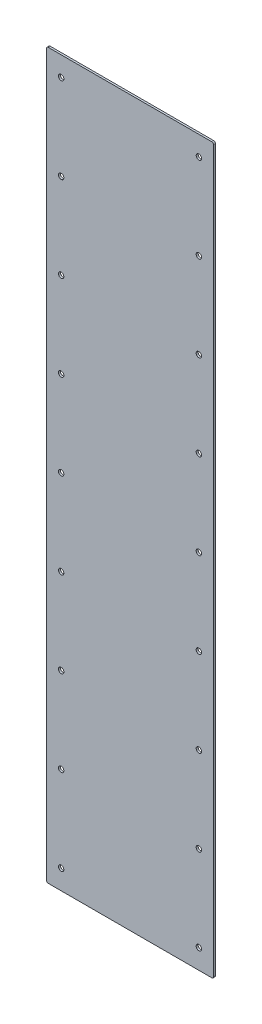
SolidWorks part; units mm, degrees
material "3.3547 (EN-AW 5083)"
ref_plane "Front Plane" through (0, 0, 0) normal (0, 0, 1) x (1, 0, 0)
ref_plane "Top Plane" through (0, 0, 0) normal (0, 1, 0) x (1, 0, 0)
ref_plane "Right Plane" through (0, 0, 0) normal (1, 0, 0) x (0, 0, -1)
sketch "Sketch1" plane through (0, 0, 0) normal (0, 0, 1) x (1, 0, 0)
  line L1 (85, -368) -> (-85, -368)
  line L2 (85, -368) -> (85, 368)
  line L3 (85, 368) -> (-85, 368)
  line L4 (-85, -368) -> (-85, 368)
  line L5 (85, -368) -> (-85, 368) construction
  line L6 (85, 368) -> (-85, -368) construction
  point P0 (0, 0)
  dimension "D1" = 736
  dimension "D2" = 170
base flange "Base-Flange1" sketch "Sketch1" thickness 2 reverse thickness direction no parameters "D1"=0.7366
hole_wizard "M5 Clearance Hole1" positions "Sketch2" profile "Sketch4" hole size "M5" standard "DIN" end condition up to next
sketch "Sketch2" plane through (0, 0, -2) normal (0, 0, -1) x (-1, 0, 0)
  line L0 (0, 0) -> (-70, 0) construction
  line L2 (-85, -368) -> (-85, 368) construction
  line L3 (-70, -348) -> (-70, 348)
  line L5 (85, -368) -> (-85, -368) construction
  point P8 (-70, -348)
  dimension "D1" = 15
  dimension "D2" = 20
sketch "Sketch4" plane through (70, -348, -2) normal (1, 0, 0) x (0, 1, 0)
  line L0 (0, 0) -> (0, 2)
  line L1 (0, 2) -> (2.75, 2)
  line L2 (2.75, 2) -> (2.75, 0)
  line L5 (2.75, 0) -> (0, 0)
  line L11 (0, -6.35) -> (0, 107.95) construction
  dimension "Thru Hole Dia." = 5.5
  dimension "Thru Hole Depth" = 2
pattern_curve "CrvPattern1" of "M5 Clearance Hole1" parameters "D1"=9, "D3"=10, "D2"=1, "D4"=10
mirror "Mirror1" about plane through (0, 0, 0) normal (1, 0, 0) of "CrvPattern1", "M5 Clearance Hole1"
fillet "Fillet1" radius 2 4 edges at (-85, 368, -1) (85, 368, -1) (85, -368, -1) (-85, -368, -1)
sketch "Bend-Lines1" [suppressed] plane through (0, 0, 0) normal (0, 1, 0) x (1, 0, 0)
sketch "Bounding-Box1" [suppressed] plane through (0, 0, 0) normal (0, 1, 0) x (1, 0, 0)
sheet metal parameters "Sheet-Metal1" thickness 2 parameters "D1"=0.7366
flat pattern "Flat-Pattern1" [suppressed]
sketch "Bend-Lines2" plane through (0, 0, 0) normal (0, 1, 0) x (1, 0, 0)
sketch3d "Bounding-Box2" [suppressed]
  line L0 (86, 372, 0) -> (86, -372, 0) construction
  line L1 (-86, 372, 0) -> (-86, -372, 0) construction
  line L2 (86, 372, 0) -> (-86, 372, 0) construction
  line L3 (86, -372, 0) -> (-86, -372, 0) construction
sheet metal parameters "Sheet-Metal2" thickness 2 parameters "D1"=0.7366
flat pattern "Flat-Pattern1"
sketch "Bend-Lines2" plane through (0, 0, 0) normal (0, 1, 0) x (1, 0, 0)
sketch3d "Bounding-Box2" [suppressed]
  line L0 (86, 372, 0) -> (86, -372, 0) construction
  line L1 (-86, 372, 0) -> (-86, -372, 0) construction
  line L2 (86, 372, 0) -> (-86, 372, 0) construction
  line L3 (86, -372, 0) -> (-86, -372, 0) construction
sheet metal parameters "Sheet-Metal3" thickness 2 parameters "D1"=0.7366
flat pattern "Flat-Pattern1"
sketch "Bend-Lines2" plane through (0, 0, 0) normal (0, 1, 0) x (1, 0, 0)
sketch3d "Bounding-Box2" [suppressed]
  line L0 (86, 372, 0) -> (86, -372, 0) construction
  line L1 (-86, 372, 0) -> (-86, -372, 0) construction
  line L2 (86, 372, 0) -> (-86, 372, 0) construction
  line L3 (86, -372, 0) -> (-86, -372, 0) construction
sheet metal parameters "Sheet-Metal4" thickness 2 parameters "D1"=0.7366
flat pattern "Flat-Pattern1"
sketch "Bend-Lines2" plane through (0, 0, 0) normal (0, 1, 0) x (1, 0, 0)
sketch3d "Bounding-Box2" [suppressed]
  line L0 (84.9996, -368, 0) -> (85, 368, 0) construction
  line L1 (-85, -367.9999, 0) -> (-84.9996, 368.0001, 0) construction
  line L2 (84.9996, -368, 0) -> (-85, -367.9999, 0) construction
  line L3 (85, 368, 0) -> (-84.9996, 368.0001, 0) construction
